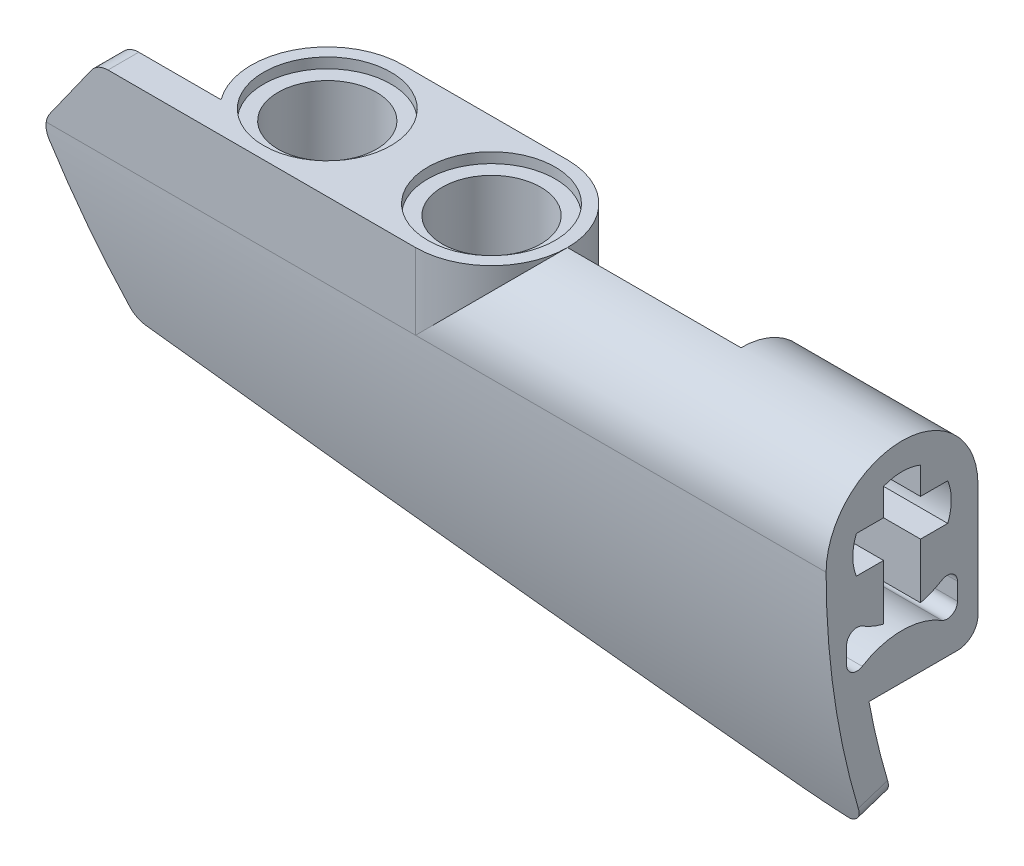
SolidWorks part; units mm, degrees
ref_plane "Front Plane" through (0, 0, 0) normal (0, 0, 1) x (1, 0, 0)
ref_plane "Top Plane" through (0, 0, 0) normal (0, 1, 0) x (1, 0, 0)
ref_plane "Right Plane" through (0, 0, 0) normal (1, 0, 0) x (0, 0, -1)
sketch "Sketch1" plane through (0, 0, 0) normal (0, 1, 0) x (1, 0, 0)
  line L0 (4, 0) -> (-4, 0) construction
  line L1 (4, -3.7) -> (-4, -3.7)
  line L2 (4, 3.7) -> (-4, 3.7)
  arc A0 (4, -3.7) -> (4, 3.7) centre (4, 0) ccw
  arc A1 (-4, 3.7) -> (-4, -3.7) centre (-4, 0) ccw
  point P2 (0, 0)
  dimension "D2" = 15.4
  dimension "D1" = 7.4
extrude "2 Block Body " add sketch "Sketch1" against normal blind 7
sketch "Sketch2" plane through (0, 0, 0) normal (1, 0, 0) x (0, 0, -1)
  line L0 (-3.7, -3.7) -> (-3.7, -10.2)
  line L1 (-3.7, -10.2) -> (3.7, -10.2)
  line L2 (3.7, -10.2) -> (3.7, -3.7)
  line L3 (3.7, 0) -> (-3.7, 0) construction
  circle A0 centre (0, -3.7) radius 3.7
  point P4 (0, 0)
  dimension "D1" = 7.4
  dimension "D2" = 10.2
extrude "Axle Body " add sketch "Sketch2" against normal blind 7.85 from offset 24 separate body contours A0 L0 L1 L2 | A0 region at (0, -8.3081, 0) region at (0, -3.7, 0)
sketch "Sketch3" plane through (24, 0, 0) normal (1, 0, 0) x (0, 0, -1)
  line L1 (2.4, -4.6) -> (-2.4, -4.6)
  line L2 (2.4, -4.6) -> (2.4, -2.8)
  line L3 (2.4, -2.8) -> (-2.4, -2.8)
  line L4 (-2.4, -4.6) -> (-2.4, -2.8)
  line L5 (2.4, -4.6) -> (-2.4, -2.8) construction
  line L6 (2.4, -2.8) -> (-2.4, -4.6) construction
  line L7 (-0.9, -6.1) -> (0.9, -6.1)
  line L8 (-0.9, -6.1) -> (-0.9, -1.3)
  line L9 (-0.9, -1.3) -> (0.9, -1.3)
  line L10 (0.9, -6.1) -> (0.9, -1.3)
  line L11 (-0.9, -6.1) -> (0.9, -1.3) construction
  line L12 (-0.9, -1.3) -> (0.9, -6.1) construction
  line L14 (2.7, -10.2) -> (2.7, -3.7)
  line L15 (2.7, -10.2) -> (2.7, -3.7)
  line L16 (0.9, -6.1) -> (0.9, -7.2889)
  line L17 (-2.7, -3.7) -> (-2.7, -10.2)
  line L18 (-2.7, -3.7) -> (-2.7, -10.2)
  line L19 (-0.9, -6.1) -> (-0.9, -7.2889)
  circle A0 centre (0, -3.7) radius 2.4
  circle A1 centre (0, -3.7) radius 3.7
  circle A2 centre (0, -11.7) radius 3.7
  dimension "D1" = 4.8
  dimension "D2" = 1.8
  dimension "D4" = 8
  dimension "D3" = 1.3
  dimension "D5" = 1
  dimension "D6" = 1
sketch "Sketch4" plane through (24, 0, 0) normal (1, 0, 0) x (0, 0, -1)
  line L0 (0, 0) -> (0, -3.7) construction
  line L1 (0, -3.7) -> (-3.7, -3.7) construction
  line L2 (-2.7, -3.7) -> (-2.7, -10.2) construction
  line L3 (-2.7, -3.7) -> (-2.7, -10.2) construction
  line L4 (-3.3, -3.7) -> (-3.3, -10.2) construction
  line L5 (-2.7, -9.1702) -> (-3.3, -9.1702) construction
  line L6 (3.7, 0) -> (-3.7, 0) construction
  line L7 (0, 0) -> (0, -1.5)
  line L8 (-1.8335, -15.4) -> (-0.408, -14.9333)
  line L9 (-3.7, -3.7) -> (-2.2, -3.7)
  circle A0 centre (0, -3.7) radius 3.7 construction
  arc A1 (0, 0) -> (-3.7, -3.7) centre (0, -3.7) ccw
  circle A2 centre (0, -11.7) radius 3.7 construction
  circle A3 centre (0, -11.7) radius 3.7 construction
  arc A4 (-3.7, -3.7) -> (-1.8335, -15.4) centre (33.9036, -3.7) ccw
  arc A5 (0, -1.5) -> (-2.2, -3.7) centre (0, -3.7) ccw
  arc A6 (-2.2, -3.7) -> (-0.408, -14.9333) centre (33.9036, -3.7) ccw
  arc M9 (3.7, -3.7) -> (-3.7, -3.7) centre (0, -3.7) ccw
  line M11 (-3.7, -10.2) -> (3.7, -10.2)
  dimension "D2" = 15.4
  dimension "D1" = 0.6
  dimension "D3" = 1.5
extrude "Fairing Top" add sketch "Sketch4" against normal up to body separate body contours A5 L7 L9 M9 region at (24, -1.7815, 1.9185)
extrude "Fairing Bottom " add sketch "Sketch4<3>" against normal blind 38.2 contours A6 A4 L8 M11 | A6 L9 A4 M11 region at (24, -6.9585, 2.7571) region at (24, -12.6997, 1.8156)
sketch "Sketch4<3>" plane through (24, 0, 0) normal (1, 0, 0) x (0, 0, -1) same geometry as "Sketch4"
sketch "Sketch5" plane through (0, 0, 0) normal (1, 0, 0) x (0, 0, -1)
  line L0 (-1.8335, -15.4) -> (-3.7, -15.4)
  line L1 (-3.7, -15.4) -> (-3.7, -3.7)
  arc A0 (-3.134, -10.2) -> (-1.8335, -15.4) centre (33.9036, -3.7) ccw construction
  arc A1 (-3.7, -3.7) -> (-1.8335, -15.4) centre (33.9036, -3.7) ccw
extrude "Fairing Side Cut " cut sketch "Sketch5" against normal through all both and the other way through all
sketch "Sketch6" plane through (-14.2, 0, 0) normal (-1, 0, 0) x (0, 0, 1)
  line L0 (3.7, 0) -> (-3.7, 0) construction
  line L1 (3.7, -3.7) -> (2.2, -3.7)
  line L2 (3.7, -3.7) -> (3.7, 0)
  line L3 (3.7, 0) -> (2.2, 0)
  line L4 (2.2, -3.7) -> (2.2, 0)
  arc A0 (2.0489, -7) -> (2.2, -3.7) centre (-33.9036, -3.7) ccw construction
  arc A1 (0.408, -14.9333) -> (2.2, -3.7) centre (-33.9036, -3.7) ccw construction
  point P7 (2.2, -3.7)
extrude "Fairing Corner" add sketch "Sketch6" against normal up to next
extrude "Axle Cut" cut sketch "Sketch3" against normal up to surface (7.85 mm away) contours L3 A0 L1 L8 | L10 A0 L8 L3 | L1 L10 L3 L8 | L8 A0 L10 L1 | A0 L3 L10 L1 | L19 A1 L16 L7 | A0 L8 L7 | A0 L7 L10 | A2 L15 A1 L18 region at (24, -3.7, -1.6222) region at (24, -5.3222, 0) region at (24, -3.7, 0) region at (24, -6.0478, -0.6767) region at (24, -3.7, 1.6222) region at (24, -2.0778, 0) region at (24, -6.732, 0) region at (24, -6.0478, 0.6767) region at (24, -7.7, 0) up to face at (16.15, -4.6819, -0.6256)
fillet "Fillet1" radius 0.5 4 edges at (20.075, -6.2298, -2.7) (20.075, -9.1702, -2.7) (20.075, -9.1702, 2.7) (20.075, -6.2298, 2.7)
sketch "Sketch7" plane through (0, 0, 0) normal (0, 1, 0) x (1, 0, 0)
  circle A0 centre (-4, 0) radius 2.4
  circle A1 centre (4, 0) radius 2.4
  dimension "D1" = 4.8
  dimension "D2" = 8
extrude "Block Holes" cut sketch "Sketch7" against normal up to surface (7 mm away) up to face at (0, -7, -1.2867)
sketch "Sketch8" plane through (0, 0, 0) normal (0, 1, 0) x (1, 0, 0)
  circle A0 centre (-4, 0) radius 2.4 construction
  circle A1 centre (4, 0) radius 2.4 construction
  circle A4 centre (-4, 0) radius 2.4
  circle A5 centre (4, 0) radius 2.4
  circle A6 centre (-4, 0) radius 3.1
  circle A7 centre (4, 0) radius 3.1
  dimension "D1" = 0.7
extrude "Rim Cuts " cut sketch "Sketch8" against normal blind 0.5
sketch "Sketch9" plane through (0, 0, 0) normal (0, 0, 1) x (1, 0, 0)
  line L0 (4, -7) -> (-4, -7) construction
  line L1 (-6.5, -8) -> (6.5, -8)
  line L2 (-6.5, -8) -> (-6.5, -7.5)
  line L3 (-6.5, -7.5) -> (6.5, -7.5)
  line L4 (6.5, -8) -> (6.5, -7.5)
  line L5 (-6.5, -8) -> (6.5, -7.5) construction
  line L6 (-6.5, -7.5) -> (6.5, -8) construction
  point P0 (0, -7.75)
  point P7 (0, 0)
  dimension "D1" = 13
  dimension "D2" = 0.5
  dimension "D3" = 0.5
extrude "Stopper " add sketch "Sketch9" against normal blind 0.5 from surface starting at face at (5.8967, -7.4747, 1.8722)
fillet "Fillet2" radius 1 1 edges at (24, -15.1666, 1.1207)
sketch "Sketch10" plane through (0, 0, 0) normal (0, 0, 1) x (1, 0, 0)
  line L0 (-14.2, 0) -> (-11.5, 0)
  line L1 (-6.9749, 0) -> (-14.2, 0) construction
  line L2 (-11.5, 0) -> (-14.2, -3.8)
  line L3 (-14.2, 0) -> (-14.2, -3.7) construction
  line L4 (-14.2, -3.8) -> (-14.2, 0)
  line L5 (-14.2, -3.8) -> (-14.2, -15.4)
  line L6 (-14.2, -15.4) -> (23, -15.4)
  line L7 (23, -15.4) -> (-10.2, -10.4)
  line L8 (-10.2, -10.4) -> (-14.2, -3.8)
  line L9 (-7.7, 0) -> (-7.7, -7) construction
  dimension "D1" = 3.8
  dimension "D2" = 3.8
  dimension "D3" = 2.5
  dimension "D4" = 10.4
extrude "Fairing Main Cut " cut sketch "Sketch10" against normal through all both and the other way through all contours L4 L2 L0 | L7 L8 L5 L6 region at (-2.9424, -12.9613, 0) region at (-13.3, -1.2667, 0)
fillet "Fillet3" radius 5 1 edges at (21.4505, -15.1666, 1.1207)
fillet "Fillet4" radius 1 4 edges at (-11.5, 0, 2.95) (-10.2, -10.4, 2.3356) (-14.2, -3.8, 2.9499) (20.075, -10.2, -3.7)
